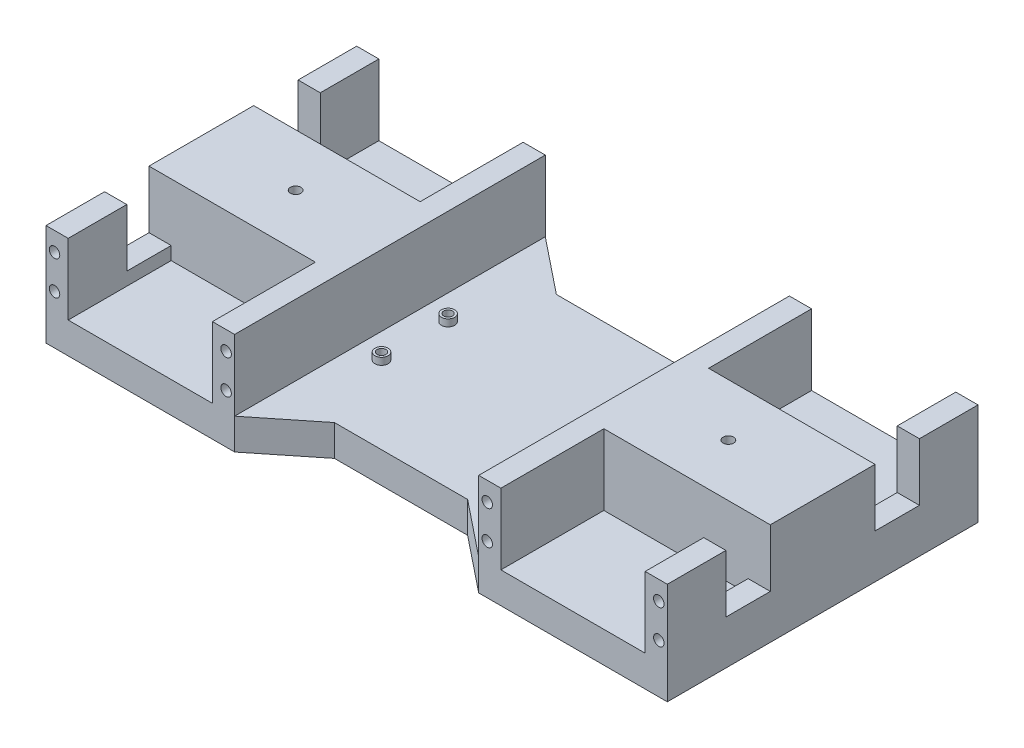
SolidWorks part; units mm, degrees
ref_plane "Front Plane" through (0, 0, 0) normal (0, 0, 1) x (1, 0, 0)
ref_plane "Top Plane" through (0, 0, 0) normal (0, 1, 0) x (1, 0, 0)
ref_plane "Right Plane" through (0, 0, 0) normal (1, 0, 0) x (0, 0, -1)
sketch "Sketch2" plane through (0, 0, 0) normal (0, 1, 0) x (1, 0, 0)
  line L0 (88.9, 0) -> (88.9, 88.9) construction
  line L1 (0, 0) -> (177.8, 0)
  line L2 (0, 0) -> (0, 88.9)
  line L3 (0, 88.9) -> (177.8, 88.9)
  line L4 (177.8, 0) -> (177.8, 88.9)
  line L5 (44.45, 12.7) -> (133.35, 12.7) construction
  line L6 (44.45, 12.7) -> (44.45, 76.2) construction
  line L7 (44.45, 76.2) -> (133.35, 76.2) construction
  line L8 (133.35, 12.7) -> (133.35, 76.2) construction
  line L9 (171.45, 0) -> (130.175, 0)
  line L10 (171.45, 0) -> (171.45, 29.464)
  line L11 (171.45, 29.464) -> (130.175, 29.464)
  line L12 (130.175, 0) -> (130.175, 29.464)
  line L17 (69.85, 12.7) -> (53.975, 12.7)
  line L18 (107.95, 12.7) -> (123.825, 12.7)
  line L19 (0, 44.45) -> (177.8, 44.45) construction
  line L24 (6.35, 29.464) -> (47.625, 29.464)
  line L25 (47.625, 0) -> (47.625, 29.464)
  line L26 (6.35, 0) -> (47.625, 0)
  line L27 (6.35, 0) -> (6.35, 29.464)
  line L28 (171.45, 59.436) -> (130.175, 59.436)
  line L29 (130.175, 88.9) -> (130.175, 59.436)
  line L30 (171.45, 88.9) -> (130.175, 88.9)
  line L31 (171.45, 88.9) -> (171.45, 59.436)
  line L36 (6.35, 88.9) -> (6.35, 59.436)
  line L37 (6.35, 88.9) -> (47.625, 88.9)
  line L38 (47.625, 88.9) -> (47.625, 59.436)
  line L39 (6.35, 59.436) -> (47.625, 59.436)
  line L44 (53.975, 0) -> (69.85, 12.7)
  line L45 (69.85, 12.7) -> (107.95, 12.7)
  line L46 (107.95, 12.7) -> (123.825, 0)
  line L47 (53.975, 88.9) -> (69.85, 76.2)
  line L48 (69.85, 76.2) -> (107.95, 76.2)
  line L49 (107.95, 76.2) -> (123.825, 88.9)
  line L50 (107.95, 76.2) -> (123.825, 76.2)
  line L51 (0, 88.9) -> (53.975, 88.9)
  line L52 (0, 88.9) -> (0, 0)
  line L53 (0, 0) -> (53.975, 0)
  line L54 (53.975, 88.9) -> (53.975, 0)
  line L55 (177.8, 0) -> (123.825, 0)
  line L56 (177.8, 0) -> (177.8, 88.9)
  line L57 (177.8, 88.9) -> (123.825, 88.9)
  line L58 (123.825, 0) -> (123.825, 88.9)
  line L59 (69.85, 76.2) -> (53.975, 76.2)
  point P9 (448.483, -253.2129)
  dimension "D1" = 88.9
  dimension "D2" = 177.8
  dimension "D3" = 63.5
  dimension "D4" = 88.9
  dimension "D5" = 31.75
  dimension "D6" = 41.275
  dimension ".9448" = 29.464
  dimension "D7" = 6.35
  dimension "D8" = 6.35
  dimension "D9" = 44.45
  dimension "D10" = 38.1
  dimension "D11" = 6.35
extrude "Boss-Extrude1" add sketch "Sketch2" along normal blind 8.89 contours L36 L39 L38 L3 | L27 L1 L25 L24 | L54 L3 L38 L39 L36 L2 L1 L27 L24 L25 | L48 L59 L54 L17 L45 L18 L58 L50 | L17 L54 L44 | L46 L58 L18 | L58 L1 L12 L11 L10 L4 L3 L31 L28 L29 | L12 L1 L10 L11 | L31 L3 L29 L28 | L50 L58 L49 | L59 L47 L54 region at (26.9875, 0, -44.45) region at (26.9875, 0, -14.732) region at (26.9875, 0, -74.168) region at (59.2667, 0, -8.4667) region at (150.8125, 0, -44.45) region at (118.5333, 0, -8.4667) region at (88.9, 0, -44.45) region at (59.2667, 0, -80.4333) region at (150.8125, 0, -14.732) region at (118.5333, 0, -80.4333) region at (150.8125, 0, -74.168)
extrude "Boss-Extrude2" add sketch "Sketch2<3>" along normal blind 29.144 contours L54 L3 L38 L39 L36 L2 L1 L27 L24 L25 | L58 L1 L12 L11 L10 L4 L3 L31 L28 L29 region at (26.9875, 0, -44.45) region at (150.8125, 0, -44.45)
sketch "Sketch2<3>" plane through (0, 0, 0) normal (0, 1, 0) x (1, 0, 0) same geometry as "Sketch2"
sketch "Sketch6" plane through (0, 29.144, 0) normal (0, 1, 0) x (1, 0, 0)
  line L0 (26.9875, 29.464) -> (26.9875, 44.45) construction
  line L1 (6.35, 29.464) -> (47.625, 29.464) construction
  line L2 (88.9, 0) -> (88.9, 88.9) construction
  line L3 (88.9, 12.7) -> (88.9, 27.7271) construction
  line L4 (69.85, 12.7) -> (107.95, 12.7) construction
  line L5 (88.9, 44.45) -> (106.0706, 44.45) construction
  line L6 (0, 44.45) -> (177.8, 44.45) construction
  circle A0 centre (26.9875, 44.45) radius 1.5
  circle A1 centre (150.8125, 44.45) radius 1.5
  dimension "D1" = 3
extrude "Cut-Extrude1" cut sketch "Sketch6" against normal blind 6.5
sketch "Sketch7" plane through (0, 0, 0) normal (0, 0, 1) x (1, 0, 0)
  line L0 (88.9, 0) -> (88.9, 26.7038) construction
  line L1 (2.4375, 14.04) -> (51.5375, 14.04) construction
  line L2 (26.9875, 14.04) -> (26.9875, 8.89) construction
  line L3 (6.35, 8.89) -> (47.625, 8.89) construction
  line L4 (47.625, 8.89) -> (6.35, 8.89) construction
  line L5 (69.85, 0) -> (107.95, 0) construction
  line L6 (150.8125, 14.04) -> (150.8125, 8.89) construction
  line L7 (175.3625, 14.04) -> (126.2625, 14.04) construction
  circle A0 centre (2.4375, 14.04) radius 1.5
  circle A1 centre (51.5375, 14.04) radius 1.5
  circle A2 centre (2.4375, 23.74) radius 1.5
  circle A3 centre (51.5375, 23.74) radius 1.5
  circle A4 centre (126.2625, 23.74) radius 1.5
  circle A5 centre (175.3625, 23.74) radius 1.5
  circle A6 centre (126.2625, 14.04) radius 1.5
  circle A7 centre (175.3625, 14.04) radius 1.5
  dimension "D1" = 49.1
  dimension "D2" = 3
  dimension "D3" = 5.15
  dimension "D4" = 9.7
extrude "Cut-Extrude2" cut sketch "Sketch7" against normal blind 6
sketch "Sketch8" plane through (0, 8.89, 0) normal (0, 1, 0) x (1, 0, 0)
  line L0 (88.9, 0) -> (88.9, 88.9) construction
  line L1 (116.713, 53.975) -> (61.087, 53.975) construction
  line L2 (116.713, 53.975) -> (116.713, 34.925) construction
  line L3 (116.713, 34.925) -> (61.087, 34.925) construction
  line L4 (61.087, 53.975) -> (61.087, 34.925) construction
  line L5 (116.713, 53.975) -> (61.087, 34.925) construction
  line L6 (116.713, 34.925) -> (61.087, 53.975) construction
  circle A0 centre (61.087, 53.975) radius 1.25
  circle A1 centre (61.087, 34.925) radius 1.25
  circle A2 centre (116.713, 34.925) radius 1.25
  circle A3 centre (116.713, 53.975) radius 1.25
  point P0 (88.9, 44.45)
  dimension "D3" = 2.5
  dimension "D1" = 19.05
  dimension "D2" = 55.626
extrude "Extrude-Thin1" add sketch "Sketch8" along normal blind 2 thin contours A1 | A0 | A3 | A2 thin type one direction wall 0.635
extrude "Cut-Extrude3" cut sketch "Sketch8<3>" against normal blind 21.78 contours A0 | A1 | A2 | A3 region at (61.087, 8.89, -53.975) region at (61.087, 8.89, -34.925) region at (116.713, 8.89, -34.925) region at (116.713, 8.89, -53.975)
sketch "Sketch8<3>" plane through (0, 8.89, 0) normal (0, 1, 0) x (1, 0, 0) same geometry as "Sketch8"
extrude "Cut-Extrude4" cut sketch "Sketch7<2>" along normal blind 6 from surface starting at face at (29.9861, 15.9162, -88.9)
sketch "Sketch7<2>" plane through (0, 0, 0) normal (0, 0, 1) x (1, 0, 0) same geometry as "Sketch7"
sketch "Sketch9" plane through (0, 0, 0) normal (-1, 0, 0) x (0, 0, 1)
  line L0 (-29.464, 29.144) -> (-29.464, 8.89) construction
  line L1 (-29.464, 12.634) -> (-16.764, 12.634)
  line L2 (-29.464, 12.634) -> (-29.464, 29.144)
  line L3 (-29.464, 29.144) -> (-16.764, 29.144)
  line L4 (-16.764, 12.634) -> (-16.764, 29.144)
  line L5 (-59.436, 12.634) -> (-72.136, 12.634)
  line L6 (-59.436, 12.634) -> (-59.436, 29.144)
  line L7 (-59.436, 29.144) -> (-72.136, 29.144)
  line L8 (-72.136, 12.634) -> (-72.136, 29.144)
  line L10 (-59.436, 29.144) -> (-59.436, 8.89) construction
  line L12 (0, 29.144) -> (-88.9, 29.144) construction
  dimension "D1" = 12.7
  dimension "D2" = 16.51
extrude "Cut-Extrude5" cut sketch "Sketch9" against normal blind 6.35
extrude "Cut-Extrude6" cut sketch "Sketch9<2>" along normal blind 6.35 from surface starting at face at (177.8, 14.572, -44.45)
sketch "Sketch9<2>" plane through (0, 0, 0) normal (-1, 0, 0) x (0, 0, 1) same geometry as "Sketch9"
sketch "Sketch10" plane through (0, 0, 0) normal (-1, 0, 0) x (0, 0, 1)
  line L0 (-29.464, 29.144) -> (-59.436, 29.144) construction
  line L1 (-54.991, 15.809) -> (-33.909, 15.809) construction
  line L2 (-54.991, 15.809) -> (-54.991, 25.461) construction
  line L3 (-54.991, 25.461) -> (-33.909, 25.461) construction
  line L4 (-33.909, 15.809) -> (-33.909, 25.461) construction
  line L5 (-44.45, 25.461) -> (-44.45, 29.144) construction
  line L7 (-72.136, 12.634) -> (-59.436, 12.634) construction
  circle A0 centre (-54.991, 25.461) radius 1
  circle A1 centre (-33.909, 25.461) radius 1
  circle A2 centre (-33.909, 15.809) radius 1
  circle A3 centre (-54.991, 15.809) radius 1
  dimension "D3" = 2
  dimension "D1" = 9.652
  dimension "D2" = 21.082
  dimension "D4" = 3.175
extrude "Cut-Extrude8" cut sketch "Sketch10" against normal blind 2
